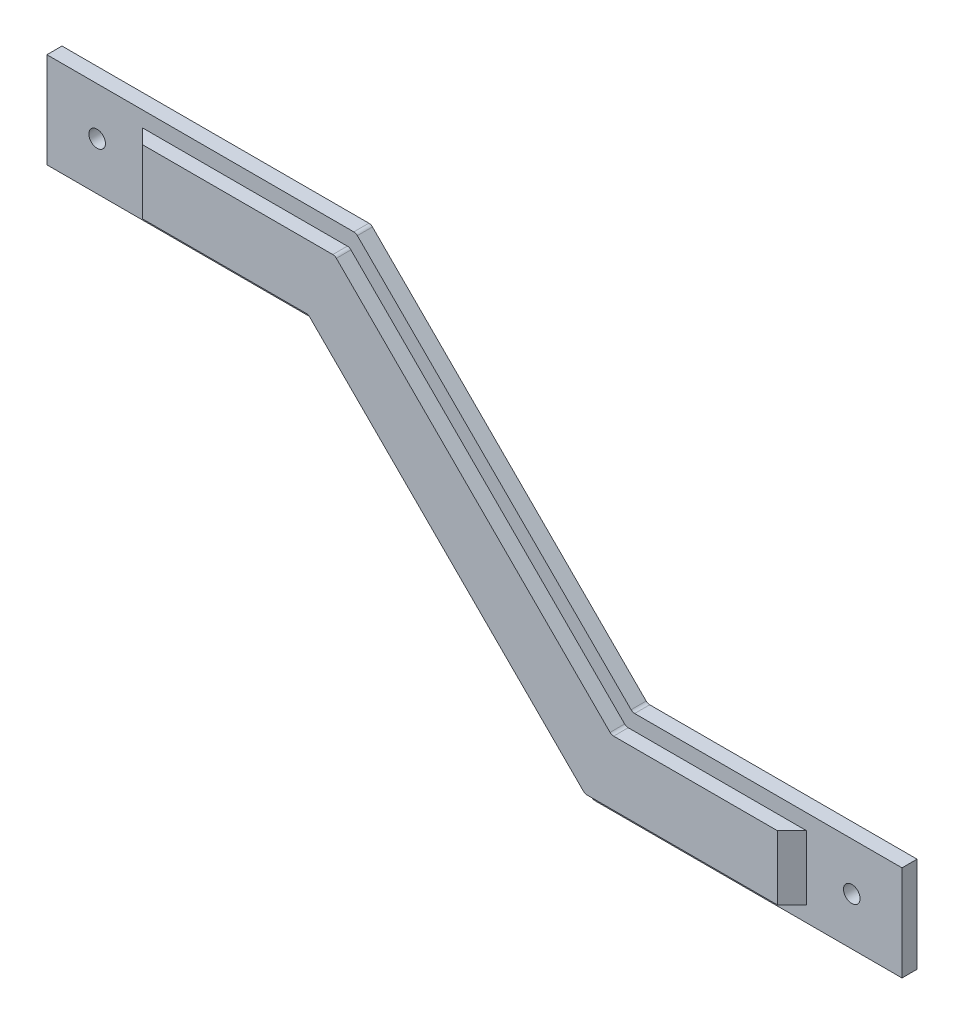
SolidWorks part; units mm, degrees
ref_plane "前视基准面" through (0, 0, 0) normal (0, 0, 1) x (1, 0, 0)
ref_plane "上视基准面" through (0, 0, 0) normal (0, 1, 0) x (1, 0, 0)
ref_plane "右视基准面" through (0, 0, 0) normal (1, 0, 0) x (0, 0, -1)
sketch "草图1" plane through (0, 0, 0) normal (0, 0, 1) x (1, 0, 0)
  line L0 (-85.15, 37.05) -> (-23.615, 37.05)
  line L1 (-23.615, 37.05) -> (31.485, -18.05)
  line L2 (31.485, -18.05) -> (85.15, -18.05)
  line L3 (85.15, -18.05) -> (85.15, -37.05)
  line L4 (85.15, -37.05) -> (23.615, -37.05)
  line L5 (23.615, -37.05) -> (-31.485, 18.05)
  line L6 (-31.485, 18.05) -> (-85.15, 18.05)
  line L7 (-85.15, 18.05) -> (-85.15, 37.05)
  line L8 (-23.615, 37.05) -> (23.615, -37.05) construction
  line L9 (-31.485, 18.05) -> (31.485, -18.05) construction
  circle A0 centre (-75.15, 27.55) radius 1.65
  circle A1 centre (75.15, -27.55) radius 1.65
  dimension "D2" = 3.3
  dimension "D1" = 19
  dimension "D3" = 150.3
  dimension "D4" = 55.1
  dimension "D5" = 9.5
  dimension "D6" = 9.5
  dimension "D7" = 135
  dimension "D8" = 19
  dimension "D9" = 10
  dimension "D10" = 10
extrude "凸台-拉伸1" add sketch "草图1" along normal blind 3
sketch "草图2" plane through (0, 0, 3) normal (0, 0, 1) x (1, 0, 0)
  line L0 (-66.15, 33.95) -> (-66.15, 21.15)
  line L1 (-66.15, 21.15) -> (-30.201, 21.15)
  line L2 (-30.201, 21.15) -> (24.899, -33.95)
  line L3 (24.899, -33.95) -> (66.15, -33.95)
  line L4 (66.15, -33.95) -> (66.15, -21.15)
  line L5 (66.15, -21.15) -> (30.201, -21.15)
  line L6 (30.201, -21.15) -> (-24.899, 33.95)
  line L7 (-24.899, 33.95) -> (-66.15, 33.95)
  line L8 (-23.615, 37.05) -> (-85.15, 37.05) construction
  line L9 (23.615, -37.05) -> (85.15, -37.05) construction
  line L10 (85.15, -37.05) -> (85.15, -18.05) construction
  line L11 (-85.15, 37.05) -> (-85.15, 18.05) construction
  line L12 (31.485, -18.05) -> (-23.615, 37.05) construction
  dimension "D1" = 12.8
  dimension "D2" = 12.8
  dimension "D3" = 3.1
  dimension "D4" = 3.1
  dimension "D5" = 19
  dimension "D6" = 19
  dimension "D7" = 12.8
extrude "凸台-拉伸2" add sketch "草图2" along normal blind 2.9
chamfer "倒角1" distance 2.9 angle 45 2 edges at (66.15, -27.55, 5.9) (-66.15, 27.55, 5.9)
fillet "圆角1" radius 1 8 edges at (-24.899, 33.95, 4.45) (-23.615, 37.05, 1.5) (31.485, -18.05, 1.5) (30.201, -21.15, 4.45) (23.615, -37.05, 1.5) (24.899, -33.95, 4.45) (-31.485, 18.05, 1.5) (-30.201, 21.15, 4.45)
